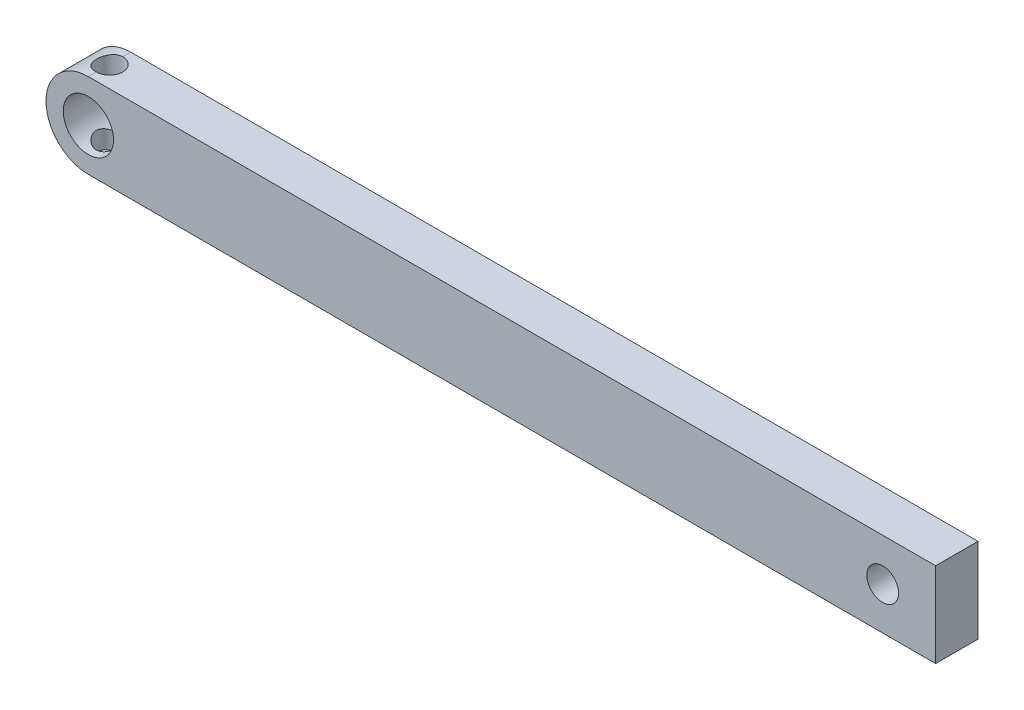
SolidWorks part; units mm, degrees
ref_plane "Front Plane" through (0, 0, 0) normal (0, 0, 1) x (1, 0, 0)
ref_plane "Top Plane" through (0, 0, 0) normal (0, 1, 0) x (1, 0, 0)
ref_plane "Right Plane" through (0, 0, 0) normal (1, 0, 0) x (0, 0, -1)
sketch "Sketch1" plane through (0, 0, 0) normal (0, 0, 1) x (1, 0, 0)
  line L0 (0, -8) -> (160, -8)
  line L1 (160, -8) -> (160, 8)
  line L2 (160, 8) -> (0, 8)
  arc A0 (0, 8) -> (0, -8) centre (0, 0) ccw
  dimension "D1" = 160
extrude "Boss-Extrude1" add sketch "Sketch1" along normal blind 8
sketch "Sketch2" plane through (0, 0, 0) normal (0, 0, 1) x (1, 0, 0)
  circle A0 centre (0, 0) radius 4.75
  circle A1 centre (150, 0) radius 3
  dimension "D1" = 9.5
  dimension "D2" = 6
extrude "Cut-Extrude1" cut sketch "Sketch2" against normal mid plane 40
sketch "Sketch3" plane through (0, 0, 0) normal (0, 0, 1) x (1, 0, 0)
  circle A0 centre (30, 0) radius 4
  dimension "D1" = 8
extrude "Cut-Extrude2" cut sketch "Sketch3" against normal mid plane 1
sketch "Sketch4" plane through (0, 0, 0) normal (0, 1, 0) x (1, 0, 0)
  line L0 (0, -8) -> (0, 0) construction
  circle A0 centre (0, -4) radius 2.5
  dimension "D1" = 5
extrude "Cut-Extrude3" cut sketch "Sketch4" against normal mid plane 40
